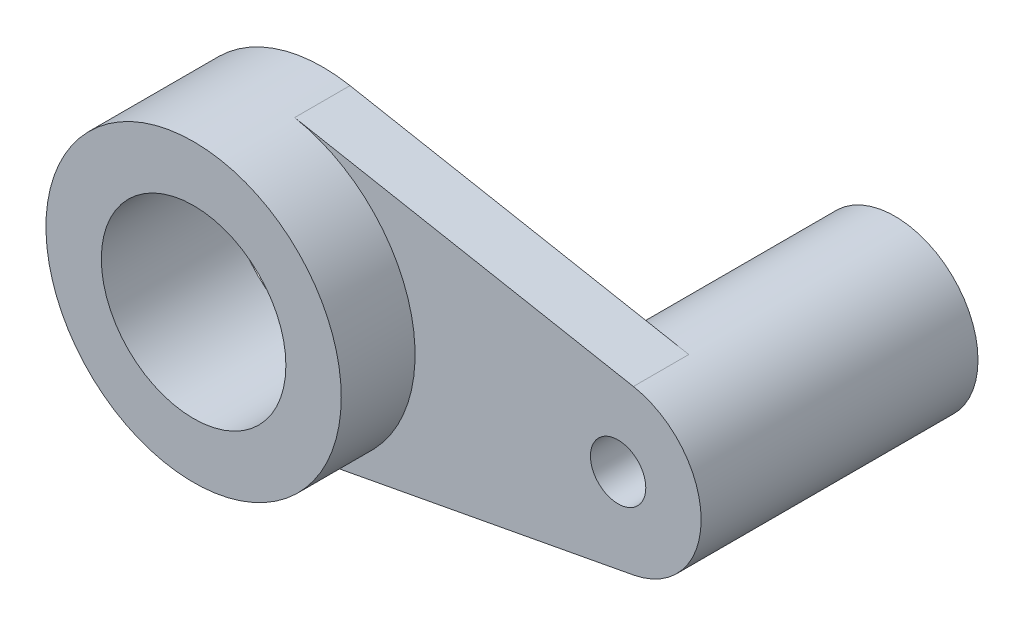
SolidWorks part; units mm, degrees
ref_plane "Alzado" through (0, 0, 0) normal (0, 0, 1) x (1, 0, 0)
ref_plane "Planta" through (0, 0, 0) normal (0, 1, 0) x (1, 0, 0)
ref_plane "Vista lateral" through (0, 0, 0) normal (1, 0, 0) x (0, 0, -1)
sketch "Croquis1" plane through (0, 0, 0) normal (0, 0, 1) x (1, 0, 0)
  line L0 (2.9474, 15.7262) -> (39.6579, 8.846)
  line L1 (2.9474, -15.7262) -> (39.6579, -8.846)
  circle A2 centre (0, 0) radius 16
  circle A3 centre (0, 0) radius 10
  circle A4 centre (38, 0) radius 3
  circle A5 centre (38, 0) radius 9
  point P7 (38, 0)
  dimension "D1" = 6
  dimension "D2" = 20
  dimension "D3" = 6
  dimension "D5" = 6
  dimension "D4" = 38
extrude "Saliente-Extruir2" add sketch "Croquis1" along normal blind 14 contours A2 A3 region at (11.9635, 9.9296, 0)
extrude "Saliente-Extruir3" add sketch "Croquis1<6>" along normal blind 6 contours A5 L0 A2 L1 | A5 A4 region at (21.925, 0, 0) region at (44.7295, 5.5854, 0)
sketch "Croquis1<6>" plane through (0, 0, 0) normal (0, 0, 1) x (1, 0, 0) same geometry as "Croquis1"
extrude "Saliente-Extruir4" add sketch "Croquis1<7>" against normal blind 24 contours A5 A4 region at (44.7295, 5.5854, 0)
sketch "Croquis1<7>" plane through (0, 0, 0) normal (0, 0, 1) x (1, 0, 0) same geometry as "Croquis1"
